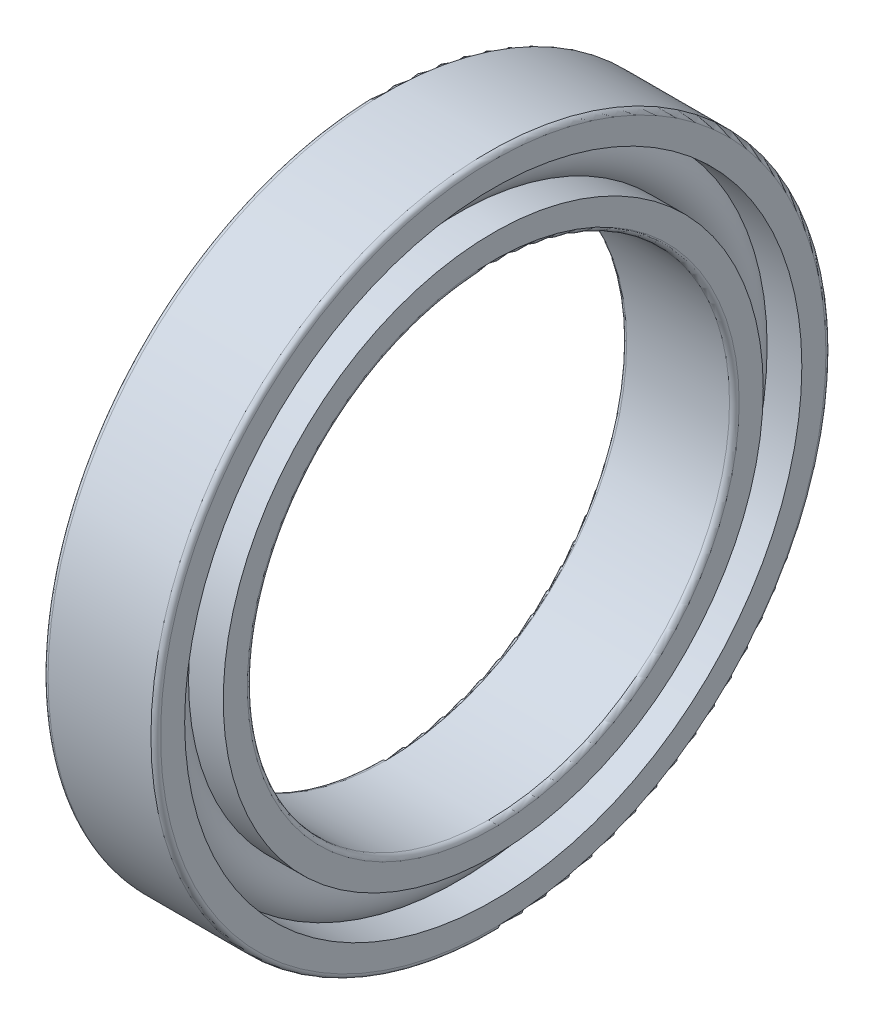
SolidWorks part; units mm, degrees
ref_plane "Plane1" through (0, 0, 0) normal (0, 0, 1) x (1, 0, 0)
ref_plane "Plane2" through (0, 0, 0) normal (0, 1, 0) x (1, 0, 0)
ref_plane "Plane3" through (0, 0, 0) normal (1, 0, 0) x (0, 0, -1)
other "Configuration Table"
sketch "Clipboard" plane through (0, 0, 0) normal (0, 0, 1) x (1, 0, 0)
  line L0 (-10, 0) -> (10, 0) construction
  line L1 (0, 0) -> (22.3471, -0.7804)
  line L2 (0, 0) -> (17.989, 0.6282)
  line L3 (0, 0) -> (22.3471, -0.7804)
  line L4 (0, 0) -> (-22.3573, -0.3902)
  dimension "BallCLRad" = 18
sketch "CagSpiSke" plane through (0, 0, 0) normal (0, 0, 1) x (1, 0, 0)
  line L0 (0.18, 17.7) -> (0.18, 18.3)
  line L1 (0.18, 18.3) -> (-0.18, 18.3)
  line L2 (-0.18, 18.3) -> (-0.18, 17.7)
  line L3 (-0.18, 17.7) -> (0.18, 17.7)
  line L4 (-20.6375, 0) -> (20.6375, 0) construction
  line L5 (0, 0) -> (0, 23.7692) construction
  dimension "OD" = 36.6
  dimension "ID" = 35.4
revolve "CageSpine" add sketch "CagSpiSke" angle 0.001 about L4 reverse direction yes
ref_axis "Axis1" through (-50, 0, 0) along (1, 0, 0)
sketch "CagBalSke" plane through (0, 0, 0) normal (0, 0, 1) x (1, 0, 0)
  line L0 (-1.98, 18) -> (1.98, 18)
  line L1 (-1.905, 18) -> (1.905, 18) construction
  line L2 (-10, 0) -> (10, 0) construction
  line L3 (0, 0) -> (0, 24) construction
  arc A0 (1.98, 18) -> (-1.98, 18) centre (0, 18) cw
  dimension "BallCLRad" = 18
revolve "CageBall" [suppressed] add sketch "CagBalSke" angle 360 about L1 reverse direction yes
pattern_circular "CageBalls" [suppressed] count 2 every 180 about axis through (-50, 0, 0) along (1, 0, 0)
sketch "CagTrmODSke" plane through (0, 0, 0) normal (0, 0, 1) x (1, 0, 0)
  line L0 (1.981, 18.3) -> (1.981, 19.981)
  line L1 (1.981, 19.981) -> (-1.981, 19.981)
  line L2 (-1.981, 19.981) -> (-1.981, 18.3)
  line L3 (-1.981, 18.3) -> (1.981, 18.3)
  line L4 (-20.6375, 0) -> (20.6375, 0) construction
  line L5 (0, 0) -> (0, 25) construction
  dimension "Width" = 3.962
  dimension "ID" = 36.6
  dimension "OD" = 39.962
revolve "CageTrimOD" [suppressed] cut sketch "CagTrmODSke" angle 360 about L4 reverse direction yes
sketch "CagTrmIDSke" plane through (0, 0, 0) normal (0, 0, 1) x (1, 0, 0)
  line L0 (1.981, 16.021) -> (1.981, 17.7)
  line L1 (1.981, 17.7) -> (-1.981, 17.7)
  line L2 (-1.981, 17.7) -> (-1.981, 16.021)
  line L3 (-1.981, 16.021) -> (1.981, 16.021)
  line L4 (-20.6375, 0) -> (20.6375, 0) construction
  line L5 (0, 0) -> (0, 25) construction
  dimension "Width" = 3.962
  dimension "ID" = 32.042
  dimension "OD" = 35.4
revolve "CageTrimID" [suppressed] cut sketch "CagTrmIDSke" angle 360 about L4 reverse direction yes
sketch "BalSimSke" plane through (0, 0, 0) normal (0, 0, 1) x (1, 0, 0)
  line L0 (-10, 0) -> (10, 0) construction
  line L1 (-10, 18) -> (10, 18) construction
  line L2 (0, 0) -> (0, 23) construction
  circle A0 centre (0, 18) radius 1.8
  dimension "BallCLRad" = 18
  dimension "Ball_diameter" = 3.6
revolve "BallsSimplified" add sketch "BalSimSke" angle 360 about L0
sketch "BalDetSke" plane through (0, 0, 0) normal (0, 0, 1) x (1, 0, 0)
  line L0 (-1.8, 18) -> (1.8, 18)
  line L1 (-1.905, 18) -> (1.905, 18) construction
  line L2 (0, 0) -> (0, 25) construction
  arc A0 (1.8, 18) -> (-1.8, 18) centre (0, 18) cw
  dimension "BallCLRad" = 18
  dimension "Ball_diameter" = 3.6
revolve "BallDetailed" [suppressed] add sketch "BalDetSke" angle 360 about L1 reverse direction yes
sketch "InnRacSke" plane through (0, 0, 0) normal (0, 0, 1) x (1, 0, 0)
  line L0 (-1.3079, 16.8) -> (-3.5, 16.8)
  line L1 (-3.5, 16.8) -> (-3.5, 15.3)
  line L2 (-3.2, 15) -> (3.2, 15)
  line L3 (3.5, 15.3) -> (3.5, 16.8)
  line L4 (3.5, 16.8) -> (1.3079, 16.8)
  line L5 (-20.6375, 0) -> (20.6375, 0) construction
  line L6 (0, 0) -> (0, 30) construction
  arc A0 (-3.5, 15.3) -> (-3.2, 15) centre (-3.2, 15.3) ccw
  arc A1 (3.2, 15) -> (3.5, 15.3) centre (3.2, 15.3) ccw
  arc A2 (1.3079, 16.8) -> (-1.3079, 16.8) centre (0, 18) cw
  dimension "BallCLRad" = 18
  dimension "Fillet_radius" = 0.3
  dimension "Ball_diameter" = 3.55
  dimension "ID" = 30
  dimension "OD" = 33.6
  dimension "Width" = 7
revolve "InnerRace" add sketch "InnRacSke" angle 360 about L5 reverse direction yes
sketch "OutRacSke" plane through (0, 0, 0) normal (0, 0, 1) x (1, 0, 0)
  line L0 (-1.3079, 19.2) -> (-3.5, 19.2)
  line L1 (-3.5, 19.2) -> (-3.5, 20.7)
  line L2 (-3.2, 21) -> (3.2, 21)
  line L3 (3.5, 20.7) -> (3.5, 19.2)
  line L4 (3.5, 19.2) -> (1.3079, 19.2)
  line L5 (-20.6375, 0) -> (20.6375, 0) construction
  line L6 (0, 0) -> (0, 30) construction
  arc A0 (-3.5, 20.7) -> (-3.2, 21) centre (-3.2, 20.7) cw
  arc A1 (3.2, 21) -> (3.5, 20.7) centre (3.2, 20.7) cw
  arc A2 (1.3079, 19.2) -> (-1.3079, 19.2) centre (0, 18) ccw
  dimension "BallCLRad" = 18
  dimension "Fillet_radius" = 0.3
  dimension "Ball_diameter" = 3.55
  dimension "Width" = 7
revolve "OuterRace" add sketch "OutRacSke" angle 360 about L5 reverse direction yes
pattern_circular "BallsDetailed" [suppressed] count 2 every 180 about axis through (-50, 0, 0) along (1, 0, 0)
equation "\"BallCLRad@Clipboard\" = ( \"OD@OutRacSke\" + \"ID@InnRacSke\" ) / 4"
equation "\"BallCLRad@BalSimSke\" = \"BallCLRad@Clipboard\""
equation "\"BallCLRad@BalDetSke\" = \"BallCLRad@Clipboard\""
equation "\"BallCLRad@InnRacSke\" = \"BallCLRad@Clipboard\""
equation "\"BallCLRad@OutRacSke\" = \"BallCLRad@Clipboard\""
equation "\"Ball_diameter@InnRacSke\" = \"Ball_diameter@BalDetSke\" - 0.05"
equation "\"Ball_diameter@OutRacSke\" = \"Ball_diameter@BalDetSke\" - 0.05"
equation "\"Ball_diameter@BalSimSke\" = \"Ball_diameter@BalDetSke\""
equation "\"Width@OutRacSke\" = \"Width@InnRacSke\""
equation "\"Fillet_radius@OutRacSke\" = \"Fillet_radius@InnRacSke\""
equation "\"Max_count@Clipboard\" = int( 3.14159265 / atn(( \"Ball_diameter@BalDetSke\" / 2) / sqr( \"BallCLRad@Clipboard\"  *  \"BallCLRad@Clipboard\" - ( \"Ball_diameter@BalDetSke\" / 2) *  ( \"Ball_diameter@BalDetSke\" / 2))))"
equation "\"Max_count@Clipboard\" = ((sgn( \"Max_count@Clipboard\" - \"Count@Clipboard\" )-1)*( \"Max_count@Clipboard\" - \"Count@Clipboard\" ))/-2+ \"Count@Clipboard\""
equation "\"Count@BallsDetailed\" = int( \"Show_count@Clipboard\" ) "
equation "\"Count@BallsDetailed\" = ((sgn( \"Count@BallsDetailed\" - \"Max_count@Clipboard\" )-1)*( \"Count@BallsDetailed\" - \"Max_count@Clipboard\" ))/-2+ \"Max_count@Clipboard\""
equation "\"Count@BallsDetailed\" = ((sgn( \"Count@BallsDetailed\" - \"Min_count@Clipboard\" )+1)*( \"Count@BallsDetailed\" - \"Min_count@Clipboard\"))/2 +\"Min_count@Clipboard\""
equation "\"Angle@BallsDetailed\" = 360.0 / \"Max_count@Clipboard\""
equation "\"BallCLRad@CagBalSke\" = \"BallCLRad@Clipboard\""
equation "\"Count@CageBalls\" = \"Count@BallsDetailed\""
equation "\"Angle@CageBalls\" = \"Angle@BallsDetailed\""
equation "\"Angle@CageSpine\" =  \"Angle@CageBalls\" * ( \"Count@CageBalls\" -1 + int( \"Count@CageBalls\" / \"Max_count@Clipboard\" ) )  + 0.001 -  int( \"Count@CageBalls\" / \"Max_count@Clipboard\" ) * 0.001"
equation "\"Angle@CageSpine\" =  \"Angle@CageSpine\" * int( \"Min_count@Clipboard\" / 2) + int(1 / \"Min_count@Clipboard\")  * 0.001"
equation "\"CageWallOD@CagBalSke\" =  \"Ball_diameter@BalDetSke\" * 1.1"
equation "\"Thickness@CagSpiSke\" =  \"Ball_diameter@BalDetSke\" * 0.1"
equation "\"OD@CagTrmODSke\" = \"BallCLRad@Clipboard\" * 2 + \"CageWallOD@CagBalSke\" + 0.002"
equation "\"ID@CagTrmODSke\" = \"BallCLRad@Clipboard\" * 2 + \"Ball_diameter@BalDetSke\" / 6"
equation "\"OD@CagTrmIDSke\" = \"BallCLRad@Clipboard\" * 2 - \"Ball_diameter@BalDetSke\" / 6"
equation "\"ID@CagTrmIDSke\" = \"BallCLRad@Clipboard\" * 2 - \"CageWallOD@CagBalSke\" + 0.002"
equation "\"OD@CagSpiSke\" = \"ID@CagTrmODSke\""
equation "\"ID@CagSpiSke\" = \"OD@CagTrmIDSke\""
equation "\"Width@CagTrmODSke\" = \"CageWallOD@CagBalSke\" + 0.002"
equation "\"Width@CagTrmIDSke\" = \"CageWallOD@CagBalSke\" + 0.002"
